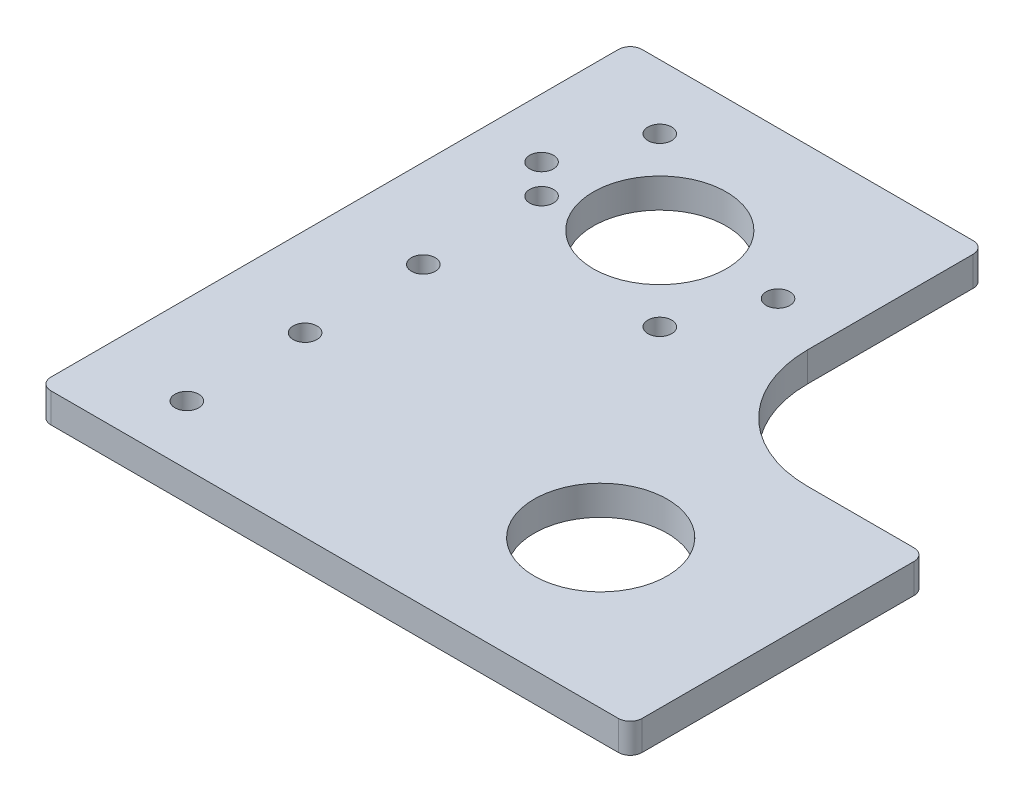
SolidWorks part; units mm, degrees
ref_plane "Front Plane" through (0, 0, 0) normal (0, 0, 1) x (1, 0, 0)
ref_plane "Top Plane" through (0, 0, 0) normal (0, 1, 0) x (1, 0, 0)
ref_plane "Right Plane" through (0, 0, 0) normal (1, 0, 0) x (0, 0, -1)
sketch "Sketch1" plane through (0, 0, 0) normal (0, 1, 0) x (1, 0, 0)
  line L1 (0, 0) -> (-127, 0)
  line L2 (0, 0) -> (0, 127)
  line L3 (0, 127) -> (-127, 127)
  line L4 (-127, 0) -> (-127, 127)
  dimension "D1" = 127
  dimension "D2" = 127
extrude "Boss-Extrude1" add sketch "Sketch1" along normal blind 6.35
sketch "Sketch2" plane through (0, 6.35, 0) normal (0, 1, 0) x (1, 0, 0)
  line L0 (0, 127) -> (-127, 127) construction
  line L1 (0, 127) -> (-50.8, 127)
  line L2 (0, 127) -> (0, 63.5)
  line L3 (0, 63.5) -> (-50.8, 63.5)
  line L4 (-50.8, 127) -> (-50.8, 63.5)
  line L5 (0, 0) -> (0, 127) construction
  dimension "D1" = 0
  dimension "D2" = 50.8
  dimension "D3" = 63.5
extrude "Cut-Extrude1" cut sketch "Sketch2" against normal through all
sketch "Sketch3" plane through (0, 6.35, 0) normal (0, 1, 0) x (1, 0, 0)
  line L0 (0, 0) -> (0, 63.5) construction
  line L1 (-50.8, 63.5) -> (0, 63.5) construction
  circle A0 centre (-38.1, 31.75) radius 14.3002
  dimension "D1" = 28.6004
  dimension "D2" = 38.1
  dimension "D3" = 31.75
extrude "Cut-Extrude2" cut sketch "Sketch3" against normal through all
sketch "Sketch4" plane through (0, 6.35, 0) normal (0, 1, 0) x (1, 0, 0)
  line L0 (-50.8, 127) -> (-127, 127) construction
  line L2 (-127, 127) -> (-127, 0) construction
  circle A0 centre (-88.9, 95.25) radius 25.4
  dimension "D1" = 50.8
  dimension "D2" = 31.75
  dimension "D4" = 38.1
sketch "Sketch5" plane through (0, 6.35, 0) normal (0, 1, 0) x (1, 0, 0)
  circle A0 centre (-114.3, 95.25) radius 2.5527
  circle A1 centre (-88.9, 95.25) radius 25.4 construction
  dimension "D1" = 5.1054
  dimension "D2" = 25.4
extrude "Cut-Extrude4" cut sketch "Sketch5" against normal through all
ref_axis "Axis1" through (-88.9, 6.35, -95.25) along (0, 1, 0)
pattern_circular "CirPattern1" count 8 every 45 about axis through (-88.9, 6.35, -95.25) along (0, 1, 0) skipping 1, 2, 5, 6 of "Cut-Extrude4"
sketch "Sketch6" plane through (0, 6.35, 0) normal (0, 1, 0) x (1, 0, 0)
  circle A0 centre (-88.9, 95.25) radius 14.3002
  dimension "D1" = 28.6004
extrude "Cut-Extrude5" cut sketch "Sketch6" against normal through all
fillet "Fillet1" radius 2.54 5 edges at (-127, 3.175, 0) (0, 3.175, 0) (0, 3.175, -63.5) (-50.8, 3.175, -127) (-127, 3.175, -127)
fillet "Fillet2" radius 25.4 1 edges at (-50.8, 3.175, -63.5)
sketch "Sketch10" plane through (0, 6.35, 0) normal (0, 1, 0) x (1, 0, 0)
  line L0 (-127, 124.46) -> (-127, 2.54) construction
  line L1 (-124.46, 0) -> (-2.54, 0) construction
  circle A0 centre (-107.95, 12.7) radius 2.5527
  dimension "D1" = 5.1054
  dimension "D2" = 19.05
  dimension "D3" = 12.7
extrude "Cut-Extrude7" cut sketch "Sketch10" against normal through all
pattern_linear "LPattern1" count 5 spacing 25.4 along (0, 0, -1) skipping (4, 0) of "Cut-Extrude7"
